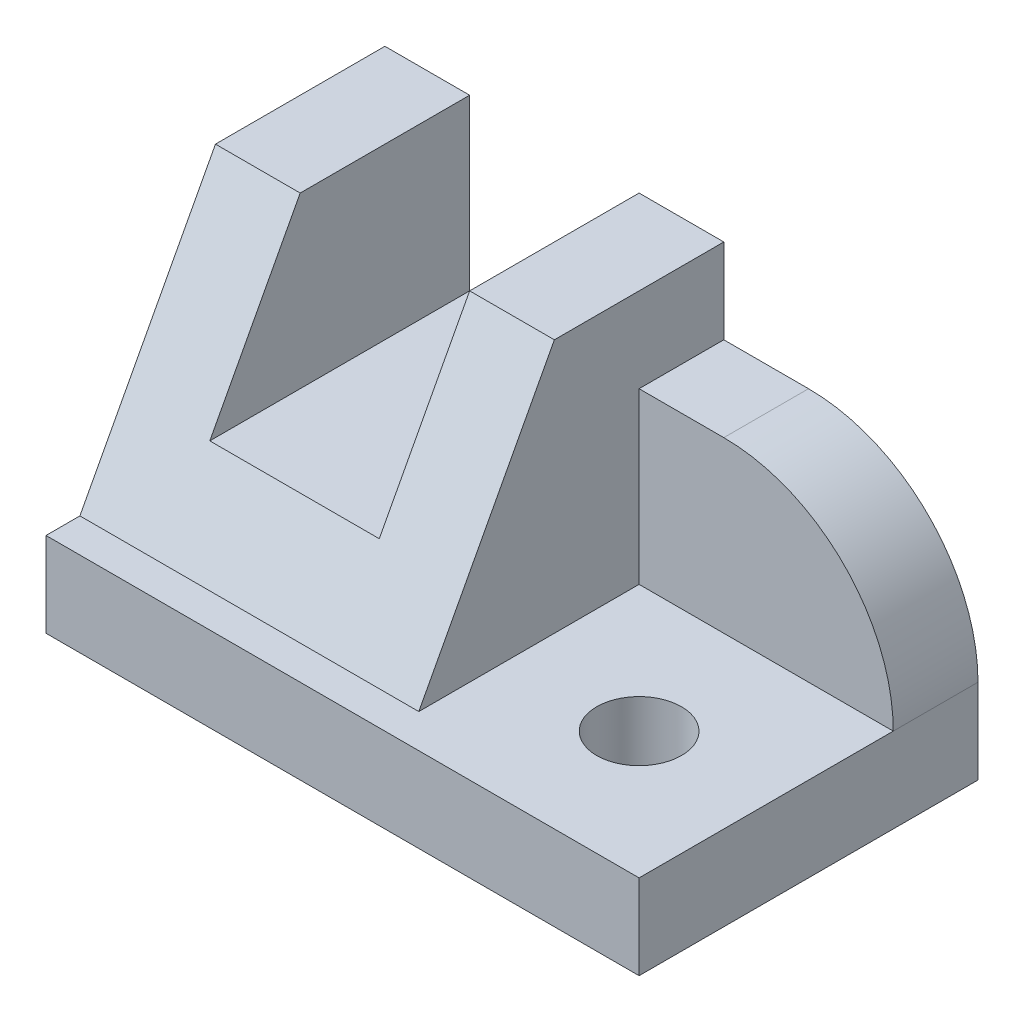
SolidWorks part; units mm, degrees
ref_plane "Front Plane" through (0, 0, 0) normal (0, 0, 1) x (1, 0, 0)
ref_plane "Top Plane" through (0, 0, 0) normal (0, 1, 0) x (1, 0, 0)
ref_plane "Right Plane" through (0, 0, 0) normal (1, 0, 0) x (0, 0, -1)
ref_plane "Plane1" through (0, 0, 0) normal (-1, 0, 0) x (0, -1, 0)
sketch "Sketch1" plane through (0, 0, 0) normal (-1, 0, 0) x (0, -1, 0)
  line L0 (-10, -4) -> (-40, -20)
  line L1 (-40, -20) -> (-10, -20)
  line L2 (-10, -20) -> (-10, -4)
  dimension "D1" = 30
  dimension "Width" = 16
extrude "Boss-Extrude1" add sketch "Sketch1" against normal blind 40
sketch "Sketch2" plane through (0, 0, -20) normal (0, 0, -1) x (-1, 0, 0)
  line L0 (-40, 40) -> (0, 40)
  line L1 (0, 40) -> (0, 10)
  line L2 (0, 10) -> (-40, 10)
  line L3 (-40, 10) -> (-40, 40)
extrude "Boss-Extrude2" add sketch "Sketch2" along normal blind 20
sketch "Sketch3" plane through (40, 0, 0) normal (1, 0, 0) x (0, 0, -1)
  line L0 (40, 10) -> (0, 10)
  line L1 (0, 10) -> (20, 40)
  line L2 (20, 40) -> (40, 40)
  line L3 (40, 40) -> (40, 10)
extrude "Boss-Extrude3" add sketch "Sketch3" along normal blind 30
sketch "Sketch4" plane through (70, 0, 0) normal (1, 0, 0) x (0, 0, -1)
  line L0 (20, 40) -> (0, 10)
  line L1 (0, 10) -> (30, 10)
  line L2 (30, 10) -> (30, 30)
  line L3 (30, 30) -> (40, 30)
  line L4 (40, 30) -> (40, 40)
  line L5 (40, 40) -> (20, 40)
extrude "Cut-Extrude1" cut sketch "Sketch4" against normal blind 30
sketch "Sketch5" plane through (0, 10, 0) normal (0, -1, 0) x (1, 0, 0)
  line L0 (70, 0) -> (70, -40)
  line L1 (70, -40) -> (0, -40)
  line L2 (0, -40) -> (0, 0)
  line L3 (0, 0) -> (70, 0)
extrude "Boss-Extrude4" add sketch "Sketch5" along normal blind 10
sketch "Sketch6" plane through (0, 0, -40) normal (0, 0, -1) x (-1, 0, 0)
  line L0 (-30, 40) -> (-30, 20)
  line L1 (-30, 20) -> (-10, 20)
  line L2 (-10, 20) -> (-10, 40)
  line L3 (-10, 40) -> (-30, 40)
extrude "Cut-Extrude2" cut sketch "Sketch6" against normal through all
hole_wizard "Ø10.0 (10) Diameter Hole1" positions "Sketch8" profile "Sketch7" hole size "Ø10.0" standard "ANSI Metric"
sketch "Sketch8" plane through (0, 0, 0) normal (0, -1, 0) x (-1, 0, 0)
  point P0 (-55, 15)
sketch "Sketch7" plane through (55, 0, -15) normal (1, 0, 0) x (0, 0, -1)
  line L0 (0, 0) -> (0, 40)
  line L1 (0, 40) -> (5, 40)
  line L2 (5, 40) -> (5, 0)
  line L5 (5, 0) -> (0, 0)
  line L11 (0, -6.35) -> (0, 107.95) construction
  dimension "Thru Hole Dia." = 10
  dimension "Thru Hole Depth" = 40
fillet "Fillet1" radius 20 1 edges at (70, 30, -35) tangent propagation no
